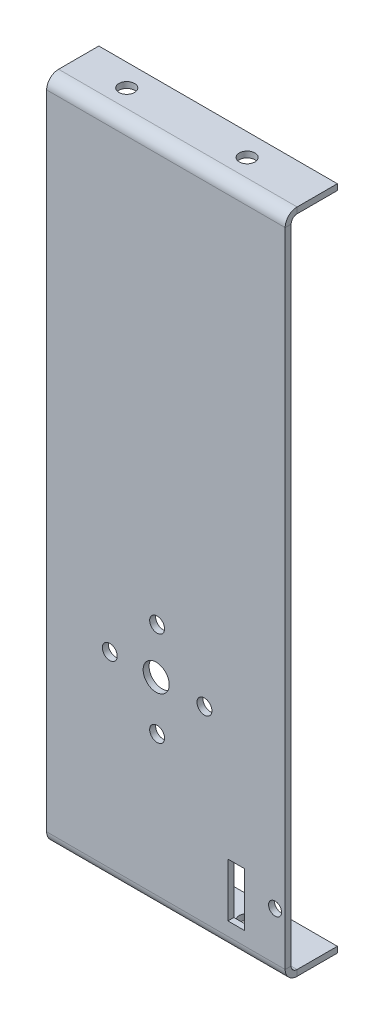
SolidWorks part; units mm, degrees
note: The reader was unsure of these and kept them because the rebuilt part matched: flange length of "Edge-Flange1", "Edge-Flange2".
material "Plain Carbon Steel"
ref_plane "Front Plane" through (0, 0, 0) normal (0, 0, 1) x (1, 0, 0)
ref_plane "Top Plane" through (0, 0, 0) normal (0, 1, 0) x (1, 0, 0)
ref_plane "Right Plane" through (0, 0, 0) normal (1, 0, 0) x (0, 0, -1)
sketch "Sketch1" plane through (0, 0, 0) normal (0, 0, 1) x (1, 0, 0)
  line L1 (0, 0) -> (64, 0)
  line L2 (0, 0) -> (0, 178.8)
  line L3 (0, 178.8) -> (64, 178.8)
  line L4 (64, 0) -> (64, 178.8)
  dimension "D1" = 64
  dimension "D2" = 178.8
base flange "Base-Flange1" sketch "Sketch1" thickness 1.6 reverse thickness direction no parameters "D1"=1.6
edge flange "Edge-Flange1" sketch "Sketch8" flange angle 90 flange length 14 flange position material inside bend radius 1.6 thickness 1.6 relief rectangular parameters "D6"=10
sketch "Sketch8" plane through (0, 0, -1.6) normal (0, -1, 0) x (-1, 0, 0)
  line L2 (-64, 0) -> (-64, 12.4)
  line L3 (-64, 12.4) -> (0, 12.4)
  line L4 (0, 12.4) -> (0, 0)
  line L7 (0, 0) -> (-64, 0) construction
  line L8 (0, 0) -> (-64, 0)
bend "EdgeBend1" bend radius 1.6 bend angle 90 parameters "D5"=1
edge flange "Edge-Flange2" sketch "Sketch11" flange angle 90 flange length 14 flange position material inside bend radius 1.6 thickness 1.6 relief rectangular parameters "D6"=10
sketch "Sketch11" plane through (0, 178.8, -1.6) normal (0, 1, 0) x (1, 0, 0)
  line L2 (0, 0) -> (0, 12.4)
  line L3 (0, 12.4) -> (64, 12.4)
  line L4 (64, 12.4) -> (64, 0)
  line L7 (64, 0) -> (0, 0) construction
  line L8 (64, 0) -> (0, 0)
bend "EdgeBend2" bend radius 1.6 bend angle 90 parameters "D5"=2
sketch "Sketch12" plane through (0, 0, 0) normal (0, -1, 0) x (1, 0, 0)
  line L0 (45.7912, -8) -> (13.4918, -8)
  circle A0 centre (45.7912, -8) radius 2.1
  circle A1 centre (13.4918, -8) radius 2.1
  dimension "D1" = 4.2
  dimension "D2" = 4.2
extrude "Cut-Extrude1" cut sketch "Sketch12" against normal blind 1000
sketch "Sketch13" plane through (0, 0, 0) normal (0, 0, 1) x (1, 0, 0)
  circle A0 centre (61.2912, 16) radius 1.75
  circle A1 centre (29.6397, 40.7686) radius 2
  circle A2 centre (42.3397, 53.4686) radius 2
  circle A3 centre (16.9397, 53.4686) radius 2
  circle A4 centre (29.6397, 66.1686) radius 2
extrude "Cut-Extrude2" cut sketch "Sketch13" against normal blind 1000 normal cut yes
sketch "Sketch14" plane through (0, 0, 0) normal (0, 0, 1) x (1, 0, 0)
  circle A0 centre (29.3846, 53.8122) radius 3.5
  dimension "D1" = 7
extrude "Cut-Extrude3" cut sketch "Sketch14" against normal blind 5 contours A0 normal cut yes
sketch "Sketch15" plane through (0, 0, 0) normal (0, 0, 1) x (1, 0, 0)
  line L1 (48.642, 21.1762) -> (53.1404, 21.1762)
  line L2 (48.642, 21.1762) -> (48.642, 6.8033)
  line L3 (48.642, 6.8033) -> (53.1404, 6.8033)
  line L4 (53.1404, 21.1762) -> (53.1404, 6.8033)
extrude "Cut-Extrude4" cut sketch "Sketch15" against normal blind 10 normal cut yes
sketch "Bend-Lines1" [suppressed] plane through (0, 0, 0) normal (0, 1, 0) x (1, 0, 0)
sketch "Bounding-Box1" [suppressed] plane through (0, 0, 0) normal (0, 1, 0) x (1, 0, 0)
sheet metal parameters "Sheet-Metal8" thickness 1.6 parameters "D1"=1.6
flat pattern "Flat-Pattern8" [suppressed]
sketch "Bend-Lines2" plane through (0, 0, 0) normal (0, 1, 0) x (1, 0, 0)
sketch3d "Bounding-Box2" [suppressed]
  line L0 (-64, 173, 0) -> (-64, 0, 0) construction
  line L1 (0, 173, 0) -> (0, 0, 0) construction
  line L2 (-64, 173, 0) -> (0, 173, 0) construction
  line L3 (-64, 0, 0) -> (0, 0, 0) construction
sheet metal parameters "Sheet-Metal9" thickness 1.6 parameters "D1"=1.6
flat pattern "Flat-Pattern8"
sketch "Bend-Lines2" plane through (0, 0, 0) normal (0, 0, 1) x (1, 0, 0)
  line L0 (0, 1.315) -> (64, 1.315) construction
  line L1 (0, 1.315) -> (64, 1.315) construction
sketch3d "Bounding-Box2" [suppressed]
  line L0 (64, 173, 0) -> (64, -11.3699, 0) construction
  line L1 (0, 173, 0) -> (0, -11.3699, 0) construction
  line L2 (64, 173, 0) -> (0, 173, 0) construction
  line L3 (64, -11.3699, 0) -> (0, -11.3699, 0) construction
bend of the flat pattern "Flatten-<EdgeBend1>1"
sheet metal parameters "Sheet-Metal10" thickness 1.6 parameters "D1"=1.6
flat pattern "Flat-Pattern8"
sketch "Bend-Lines2" plane through (0, 0, 0) normal (0, 0, 1) x (1, 0, 0)
  line L0 (0, 1.315) -> (64, 1.315) construction
  line L1 (0, 1.315) -> (64, 1.315) construction
  line L2 (64, 177.485) -> (0, 177.485) construction
  line L3 (64, 177.485) -> (0, 177.485) construction
sketch3d "Bounding-Box2" [suppressed]
  line L0 (64, 190.1699, 0) -> (64, -11.3699, 0) construction
  line L1 (0, 190.1699, 0) -> (0, -11.3699, 0) construction
  line L2 (64, 190.1699, 0) -> (0, 190.1699, 0) construction
  line L3 (64, -11.3699, 0) -> (0, -11.3699, 0) construction
bend of the flat pattern "Flatten-<EdgeBend1>1"
bend of the flat pattern "Flatten-<EdgeBend2>1"
sheet metal parameters "Sheet-Metal11" thickness 1.6 parameters "D1"=1.6
flat pattern "Flat-Pattern8"
sketch "Bend-Lines2" plane through (0, 0, 0) normal (0, 0, 1) x (1, 0, 0)
  line L0 (0, 1.315) -> (64, 1.315) construction
  line L1 (0, 1.315) -> (64, 1.315) construction
  line L2 (64, 177.485) -> (0, 177.485) construction
  line L3 (64, 177.485) -> (0, 177.485) construction
sketch3d "Bounding-Box2" [suppressed]
  line L0 (64, 190.1699, 0) -> (64, -11.3699, 0) construction
  line L1 (0, 190.1699, 0) -> (0, -11.3699, 0) construction
  line L2 (64, 190.1699, 0) -> (0, 190.1699, 0) construction
  line L3 (64, -11.3699, 0) -> (0, -11.3699, 0) construction
bend of the flat pattern "Flatten-<EdgeBend1>1"
bend of the flat pattern "Flatten-<EdgeBend2>1"
sheet metal parameters "Sheet-Metal12" thickness 1.6 parameters "D1"=1.6
flat pattern "Flat-Pattern8"
sketch "Bend-Lines2" plane through (0, 0, 0) normal (0, 0, 1) x (1, 0, 0)
  line L0 (0, 1.315) -> (64, 1.315) construction
  line L1 (0, 1.315) -> (64, 1.315) construction
  line L2 (64, 177.485) -> (0, 177.485) construction
  line L3 (64, 177.485) -> (0, 177.485) construction
sketch3d "Bounding-Box2" [suppressed]
  line L0 (64, 190.1699, 0) -> (64, -11.3699, 0) construction
  line L1 (0, 190.1699, 0) -> (0, -11.3699, 0) construction
  line L2 (64, 190.1699, 0) -> (0, 190.1699, 0) construction
  line L3 (64, -11.3699, 0) -> (0, -11.3699, 0) construction
bend of the flat pattern "Flatten-<EdgeBend1>1"
bend of the flat pattern "Flatten-<EdgeBend2>1"
sheet metal parameters "Sheet-Metal13" thickness 1.6 parameters "D1"=1.6
flat pattern "Flat-Pattern8"
sketch "Bend-Lines2" plane through (0, 0, 0) normal (0, 0, 1) x (1, 0, 0)
  line L0 (0, 1.315) -> (64, 1.315) construction
  line L1 (0, 1.315) -> (64, 1.315) construction
  line L2 (64, 177.485) -> (0, 177.485) construction
  line L3 (64, 177.485) -> (0, 177.485) construction
sketch3d "Bounding-Box2" [suppressed]
  line L0 (64, 190.1699, 0) -> (64, -11.3699, 0) construction
  line L1 (0, 190.1699, 0) -> (0, -11.3699, 0) construction
  line L2 (64, 190.1699, 0) -> (0, 190.1699, 0) construction
  line L3 (64, -11.3699, 0) -> (0, -11.3699, 0) construction
bend of the flat pattern "Flatten-<EdgeBend1>1"
bend of the flat pattern "Flatten-<EdgeBend2>1"
sheet metal parameters "Sheet-Metal14" thickness 1.6 parameters "D1"=1.6
flat pattern "Flat-Pattern8"
sketch "Bend-Lines2" plane through (0, 0, 0) normal (0, 0, 1) x (1, 0, 0)
  line L0 (0, 1.315) -> (64, 1.315) construction
  line L1 (0, 1.315) -> (64, 1.315) construction
  line L2 (64, 177.485) -> (0, 177.485) construction
  line L3 (64, 177.485) -> (0, 177.485) construction
sketch3d "Bounding-Box2" [suppressed]
  line L0 (64, 190.1699, 0) -> (64, -11.3699, 0) construction
  line L1 (0, 190.1699, 0) -> (0, -11.3699, 0) construction
  line L2 (64, 190.1699, 0) -> (0, 190.1699, 0) construction
  line L3 (64, -11.3699, 0) -> (0, -11.3699, 0) construction
bend of the flat pattern "Flatten-<EdgeBend1>1"
bend of the flat pattern "Flatten-<EdgeBend2>1"
